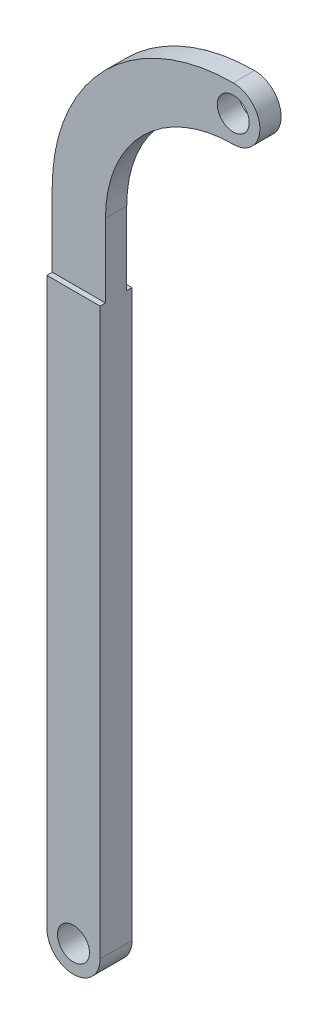
SolidWorks part; units mm, degrees
material "7075-O (SS)"
ref_plane "前视基准面" through (0, 0, 0) normal (0, 0, 1) x (1, 0, 0)
ref_plane "上视基准面" through (0, 0, 0) normal (0, 1, 0) x (1, 0, 0)
ref_plane "右视基准面" through (0, 0, 0) normal (1, 0, 0) x (0, 0, -1)
sketch "草图1" plane through (0, 0, 0) normal (0, 0, 1) x (1, 0, 0)
  line L0 (-2.5, 0) -> (-2.5, 60)
  line L1 (2.5, 0) -> (2.5, 60)
  line L3 (14.5, 77) -> (14.5, 72) construction
  circle A0 centre (0, 0) radius 1.5
  arc A1 (-2.5, 0) -> (2.5, 0) centre (0, 0) ccw
  arc A2 (14.5, 72) -> (2.5, 60) centre (14.5, 60) ccw
  arc A3 (14.5, 77) -> (-2.5, 60) centre (14.5, 60) ccw
  arc A4 (14.5, 72) -> (14.5, 77) centre (14.5, 74.5) ccw
  circle A5 centre (14.5, 74.5) radius 1.5
extrude "凸台-拉伸1" add sketch "草图1" along normal blind 3
sketch "草图2" plane through (0, 0, 0) normal (1, 0, 0) x (0, 0, -1)
  line L0 (-0.5, 77) -> (0, 77)
  line L1 (-3, 77) -> (0, 77) construction
  line L2 (-0.5, 77) -> (-0.5, 53.1001)
  line L3 (-0.5, 53.1001) -> (0, 53.1001)
  line L4 (0, 0) -> (0, 60) construction
  line L5 (0, 53.1001) -> (0, 77)
  line L6 (-3.0848, 77) -> (-2.4953, 77)
  line L7 (-3.0848, 77) -> (-3.0848, 53.1001)
  line L8 (-3.0848, 53.1001) -> (-2.4953, 53.1001)
  line L9 (-2.4953, 53.1001) -> (-2.4953, 77)
  point P13 (0, 0)
extrude "切除-拉伸1" cut sketch "草图2" against normal through all and the other way through all
